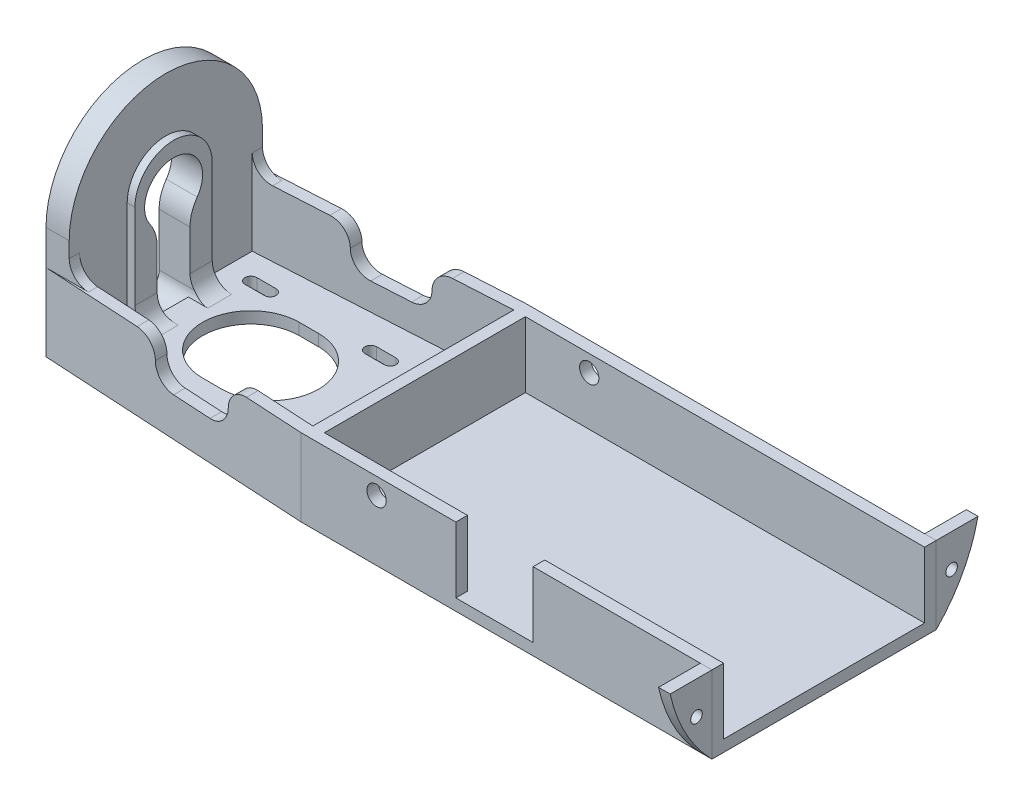
SolidWorks part; units mm, degrees
ref_plane "Front Plane" through (0, 0, 0) normal (0, 0, 1) x (1, 0, 0)
ref_plane "Top Plane" through (0, 0, 0) normal (0, 1, 0) x (1, 0, 0)
ref_plane "Right Plane" through (0, 0, 0) normal (1, 0, 0) x (0, 0, -1)
sketch "Sketch2" plane through (0, 0, 0) normal (0, 1, 0) x (1, 0, 0)
  line L0 (-119.25, 25) -> (-119.25, -25)
  line L1 (-49.25, -29) -> (57, -29)
  line L2 (-49.25, -29) -> (-49.25, 29)
  line L3 (-49.25, 29) -> (57, 29)
  line L4 (57, -29) -> (57, 29)
  line L6 (60, 12) -> (60, -39) construction
  line L7 (-119.25, -25) -> (-49.25, -29)
  line L8 (-119.25, 25) -> (-49.25, 29)
  line L9 (-46.25, -23.4) -> (-46.25, 23.4) construction
  line L10 (-46.25, 23.4) -> (-46.25, -23.4) construction
  point P0 (0, 0)
  point P8 (-49.25, 0)
  point P9 (-119.25, 0)
  point P14 (-46.25, 0)
  dimension "D1" = 3
  dimension "D2" = 58
  dimension "D3" = 50
  dimension "D4" = 70
  dimension "D5" = 3
extrude "Boss-Extrude1" add sketch "Sketch2" along normal blind 3 contours L8 L0 L7 L2 | L1 L4 L3 L2 region at (-83.3858, 0, 0) region at (3.875, 0, 0)
sketch "Sketch3" plane through (0, 0, 0) normal (0, -1, 0) x (1, 0, 0)
  line L0 (-49.25, -29) -> (57, -29) construction
  line L1 (-49.25, 29) -> (-46.25, 29)
  line L2 (-49.25, 29) -> (-49.25, -29)
  line L3 (-49.25, -29) -> (-46.25, -29)
  line L4 (-46.25, 29) -> (-46.25, -29)
  line L5 (57, 29) -> (57, -29) construction
  line L6 (-46.25, 29) -> (57, 29)
  line L7 (-46.25, 29) -> (-46.25, 26)
  line L8 (-46.25, 26) -> (57, 26)
  line L9 (57, 29) -> (57, 26)
  line L10 (-119.25, 25) -> (-49.25, 29) construction
  line L11 (57, -29) -> (-46.25, -29)
  line L12 (57, -29) -> (57, -26)
  line L13 (57, -26) -> (-46.25, -26)
  line L14 (-46.25, -29) -> (-46.25, -26)
  line L15 (-119.25, -21.9951) -> (-49.25, -25.9951)
  line L16 (-119.25, -25) -> (-49.25, -29) construction
  line L17 (-119.25, -25) -> (-119.25, 25) construction
  line L18 (-119.25, 21.9951) -> (-119.25, 25)
  line L19 (-119.25, 25) -> (-49.25, 29)
  line L20 (-49.25, 29) -> (-49.25, 25.9951)
  line L21 (-119.25, -21.9951) -> (-119.25, -25)
  line L22 (-119.25, -25) -> (-49.25, -29)
  line L23 (-49.25, -25.9951) -> (-49.25, -29)
  line L29 (-119.25, 21.9951) -> (-49.25, 25.9951)
  line M3 (-49.25, -29) -> (57, -29)
  line M4 (57, -29) -> (57, 29)
  line M5 (57, 29) -> (-49.25, 29)
  dimension "D1" = 3
  dimension "D2" = 3
  dimension "D3" = 3
  dimension "D4" = 3
  dimension "D5" = 3
extrude "Boss-Extrude2" add sketch "Sketch3" against normal blind 20 contours L4 L8 M4 M5 | L4 L2 M5 M3 | L13 L4 M4 M3 region at (-47.75, 0, 0) region at (5.375, 0, 27.5) region at (5.375, 0, -27.5)
sketch "Sketch4" plane through (0, 0, 0) normal (0, -1, 0) x (1, 0, 0)
  line L0 (-119.25, -25) -> (-119.25, 25)
  line L1 (-119.25, -25) -> (-113.25, -25)
  line L2 (-119.25, 25) -> (-113.25, 25)
  line L3 (-113.25, -25) -> (-113.25, 25)
  dimension "D1" = 6
extrude "Boss-Extrude3" add sketch "Sketch4" against normal blind 29
sketch "Sketch5" plane through (0, 3, 0) normal (0, 1, 0) x (1, 0, 0)
  line L0 (-49.25, 25.9951) -> (-113.25, 22.338)
  line L1 (-49.25, 29) -> (-49.25, -29) construction
  line L2 (-113.25, -25) -> (-113.25, 25) construction
  line L3 (-113.25, 22.338) -> (-119.25, 25)
  line L4 (-119.25, 25) -> (-49.25, 29)
  line L5 (-49.25, 29) -> (-49.25, 25.9951)
  line L6 (-49.25, -25.9951) -> (-113.25, -22.338)
  line L7 (-113.25, -22.338) -> (-119.25, -25)
  line L8 (-119.25, -25) -> (-49.25, -29)
  line L9 (-49.25, -29) -> (-49.25, -25.9951)
  dimension "D1" = 3
  dimension "D2" = 3
extrude "Boss-Extrude4" add sketch "Sketch5" along normal up to surface (17 mm away) up to face at (4.625, 20, 0)
sketch "Sketch6" plane through (-119.25, 0, 0) normal (-1, 0, 0) x (0, 0, 1)
  line L0 (25, 29) -> (-25, 29) construction
  circle A0 centre (0, 29) radius 25
extrude "Boss-Extrude5" add sketch "Sketch6" against normal up to surface (6 mm away) up to face at (-113.25, 18, 0)
sketch "Sketch7" plane through (-119.25, 0, 0) normal (-1, 0, 0) x (0, 0, 1)
  circle A0 centre (0, 29) radius 3.1
  point P21 (0, 30)
  dimension "D1" = 6.2
sketch "Sketch19" plane through (-113.25, 0, 0) normal (1, 0, 0) x (0, 0, -1)
  line L0 (25, 0) -> (-25, 0) construction
  line L1 (-10, 30) -> (-10, 0)
  line L2 (10, 30) -> (10, 0)
  line L3 (-10, 0) -> (10, 0)
  arc A0 (10, 30) -> (-10, 30) centre (0, 30) ccw
  circle A1 centre (0, 30) radius 1.5
  point P11 (0, 0)
  dimension "D1" = 20
  dimension "D2" = 3
extrude "Boss-Extrude9" add sketch "Sketch19" along normal blind 2
sketch "Sketch10" plane through (0, 0, 29) normal (0, 0, 1) x (1, 0, 0)
  circle A0 centre (-29.74, 15.6975) radius 2.5
  circle A1 centre (-29.74, 15.6975) radius 1.7272 construction
  dimension "D1" = 5
extrude "Cut-Extrude3" cut sketch "Sketch10" against normal through all both and the other way through all
sketch "Sketch16" plane through (57, 0, 0) normal (1, 0, 0) x (0, 0, -1)
  line L0 (-29, 20) -> (-39.8121, 20)
  line L1 (-29, 0) -> (-29, 20)
  line L2 (29, 20) -> (39.8121, 20)
  line L3 (29, 0) -> (29, 20)
  arc A0 (-39.8121, 20) -> (-29, 0) centre (0, 28.6) ccw
  circle A1 centre (-33, 11.5) radius 1.5 construction
  arc A2 (29, 0) -> (39.8121, 20) centre (0, 28.6) ccw
  circle A3 centre (-33, 11.5) radius 1.5
  arc A4 (-58.5297, 41.8011) -> (58.5297, 41.8011) centre (0, 28.6) ccw construction
  circle A5 centre (33, 11.5) radius 1.5
  circle A7 centre (33, 11.5) radius 1.5 construction
extrude "Boss-Extrude8" add sketch "Sketch16" against normal blind 3 separate body
sketch "Sketch18" plane through (0, 0, 29) normal (0, 0, 1) x (1, 0, 0)
  line L0 (57, 20) -> (-49.25, 20) construction
  line L1 (10.75, 20) -> (-9.25, 20)
  line L2 (10.75, 20) -> (10.75, 3)
  line L3 (10.75, 3) -> (-9.25, 3)
  line L4 (-9.25, 20) -> (-9.25, 3)
  line L5 (10.75, 5.4) -> (10.75, 17.4) construction
  line L6 (-49.25, 0) -> (57, 0) construction
  dimension "D1" = 20
  dimension "D2" = 3
extrude "Cut-Extrude5" cut sketch "Sketch18" against normal up to next (3 mm away)
sketch "Sketch20" plane through (-119.25, 0, 0) normal (-1, 0, 0) x (0, 0, 1)
  line L0 (0, 28.6) -> (0, 4.85)
  line L1 (-4.25, 28.6) -> (-4.25, 4.85)
  line L2 (4.25, 28.6) -> (4.25, 4.85)
  circle A0 centre (0, 28.6) radius 7.5
  arc A1 (-4.25, 28.6) -> (4.25, 28.6) centre (0, 28.6) cw
  arc A2 (-4.25, 4.85) -> (4.25, 4.85) centre (0, 4.85) ccw
  arc A4 (29, 0) -> (39.8121, 20) centre (0, 28.6) ccw construction
  dimension "D1" = 15
  dimension "D4" = 23.75
  dimension "D2" = 4.25
  dimension "D3" = 4.25
extrude "Cut-Extrude6" cut sketch "Sketch20" against normal blind 8 contours L1 A1 L2 A0 | A1 L1 A0 L2 | L1 A2 L2 A0 region at (-119.25, 32.705, 0) region at (-119.25, 25.5102, -4.453) region at (-119.25, 21.2141, -2.2947)
fillet "Fillet1" radius 10 2 edges at (-115.25, 22.4204, 4.25) (-115.25, 22.4204, -4.25)
sketch "Sketch25" plane through (0, 0, 29) normal (0, 0, 1) x (1, 0, 0)
  line L0 (-119.25, 0) -> (-49.25, 0) construction
  line L1 (-69.25, 20) -> (-89.25, 20)
  line L2 (-69.25, 20) -> (-69.25, 10)
  line L3 (-69.25, 10) -> (-89.25, 10)
  line L4 (-89.25, 20) -> (-89.25, 10)
  line L5 (-49.25, 20) -> (-119.25, 20) construction
  line L6 (-49.25, 20) -> (-49.25, 0) construction
  dimension "D1" = 20
  dimension "D2" = 10
  dimension "D3" = 20
extrude "Cut-Extrude10" cut sketch "Sketch25" against normal through all
sketch "Sketch26" plane through (0, 0, 0) normal (0, -1, 0) x (-1, 0, 0)
  line L1 (70.75, -15.5) -> (71.725, -15.5) construction
  line L2 (70.75, -13.975) -> (75.75, -13.975)
  line L3 (70.75, -17.025) -> (75.75, -17.025)
  line L4 (86.25, 0) -> (91.25, 0) construction
  line L7 (101.75, -15.5) -> (106.75, -15.5) construction
  line L8 (101.75, -13.975) -> (106.75, -13.975)
  line L9 (101.75, -17.025) -> (106.75, -17.025)
  line L10 (70.75, 15.5) -> (75.75, 15.5) construction
  line L11 (70.75, 17.025) -> (75.75, 17.025)
  line L12 (70.75, 13.975) -> (75.75, 13.975)
  line L13 (101.75, 15.5) -> (106.75, 15.5) construction
  line L14 (101.75, 17.025) -> (106.75, 17.025)
  line L15 (101.75, 13.975) -> (106.75, 13.975)
  line L16 (86.25, 12.5) -> (91.25, 12.5)
  line L17 (86.25, -12.5) -> (91.25, -12.5)
  line L18 (74.775, -15.5) -> (75.75, -15.5) construction
  line L19 (119.25, 25) -> (119.25, -25) construction
  arc A5 (70.75, -13.975) -> (70.75, -17.025) centre (70.75, -15.5) ccw
  arc A6 (75.75, -17.025) -> (75.75, -13.975) centre (75.75, -15.5) ccw
  arc A9 (101.75, -13.975) -> (101.75, -17.025) centre (101.75, -15.5) ccw
  arc A10 (106.75, -17.025) -> (106.75, -13.975) centre (106.75, -15.5) ccw
  arc A11 (70.75, 17.025) -> (70.75, 13.975) centre (70.75, 15.5) ccw
  arc A12 (75.75, 13.975) -> (75.75, 17.025) centre (75.75, 15.5) ccw
  arc A13 (101.75, 17.025) -> (101.75, 13.975) centre (101.75, 15.5) ccw
  arc A14 (106.75, 13.975) -> (106.75, 17.025) centre (106.75, 15.5) ccw
  arc A15 (86.25, 12.5) -> (86.25, -12.5) centre (86.25, 0) ccw
  arc A16 (91.25, -12.5) -> (91.25, 12.5) centre (91.25, 0) ccw
  point P4 (73.25, -15.5)
  point P8 (88.75, 0)
  point P15 (88.75, 0)
  point P21 (73.25, 15.5)
  point P23 (88.75, 0)
  point P32 (104.25, -15.5)
  point P44 (104.25, 15.5)
  dimension "D2" = 15.5
  dimension "D3" = 15.5
  dimension "D4" = 30.5
  dimension "D8" = 1.525
  dimension "D9" = 5
  dimension "D10" = 5
  dimension "D12" = 1.525
  dimension "D13" = 5
  dimension "D14" = 1.525
  dimension "D15" = 5
  dimension "D16" = 12.5
  dimension "D17" = 5
extrude "Cut-Extrude11" cut sketch "Sketch26" against normal up to next (3 mm away)
fillet "Fillet2" radius 5 8 edges at (-89.25, 10, 25.2118) (-69.25, 10, 26.3547) (-69.25, 10, -26.3547) (-89.25, 10, -25.2118) (-69.25, 20, 26.3547) (-69.25, 20, -26.3547) (-89.25, 20, 25.2118) (-89.25, 20, -25.2118)
fillet "Fillet3" radius 5 4 edges at (-111.25, 3, 6.9131) (-111.25, 3, -6.9131) (-113.25, 20, -23.669) (-113.25, 20, 23.669)
